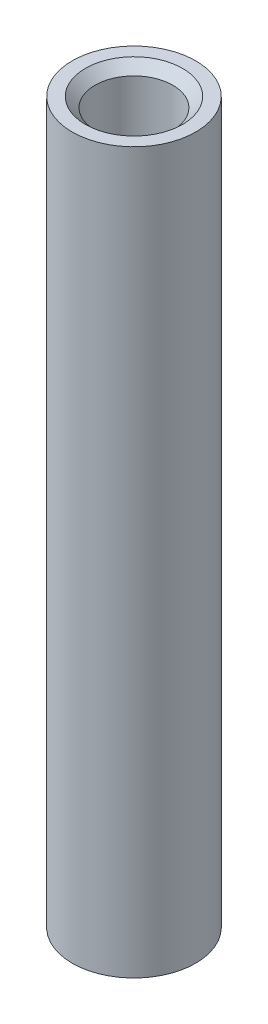
SolidWorks part; units mm, degrees
material "Natural Rubber"
ref_plane "Front Plane" through (0, 0, 0) normal (0, 0, 1) x (1, 0, 0)
ref_plane "Top Plane" through (0, 0, 0) normal (0, 1, 0) x (1, 0, 0)
ref_plane "Right Plane" through (0, 0, 0) normal (1, 0, 0) x (0, 0, -1)
sketch "Sketch1" plane through (0, 0, 0) normal (0, 1, 0) x (1, 0, 0)
  circle A0 centre (0, 0) radius 31.75
  circle A1 centre (0, 0) radius 20
  dimension "D1" = 63.5
  dimension "D2" = 40
extrude "Boss-Extrude1" add sketch "Sketch1" along normal blind 370.2
chamfer "Chamfer2" distance 5 angle 45 1 edges at (0, 370.2, 20)
